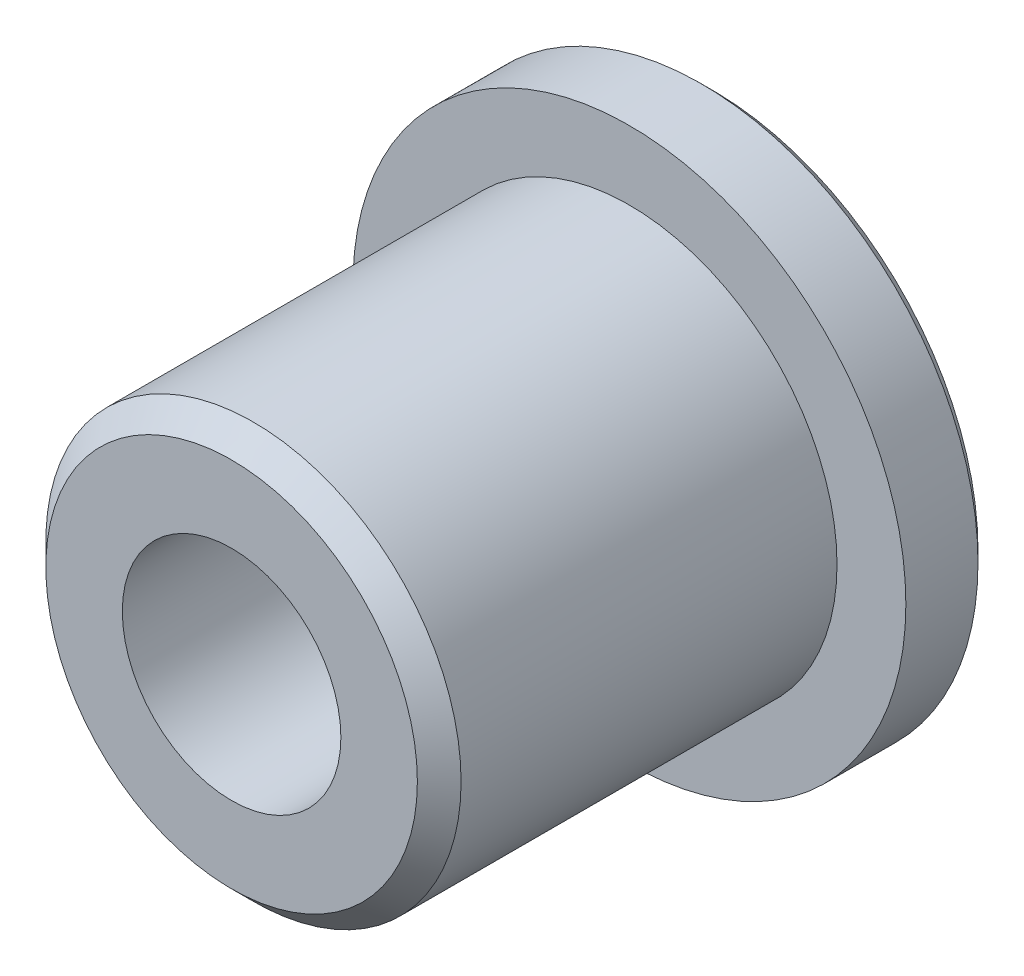
SolidWorks part; units mm, degrees
ref_plane "정면" through (0, 0, 0) normal (0, 0, 1) x (1, 0, 0)
ref_plane "윗면" through (0, 0, 0) normal (0, 1, 0) x (1, 0, 0)
ref_plane "우측면" through (0, 0, 0) normal (1, 0, 0) x (0, 0, -1)
sketch "스케치1" plane through (0, 0, 0) normal (0, 0, 1) x (1, 0, 0)
  circle A0 centre (0, 0) radius 5.875
  circle A1 centre (0, 0) radius 12.65
  dimension "D1" = 11.75
  dimension "D2" = 25.3
extrude "보스-돌출1" add sketch "스케치1" along normal blind 2
sketch "스케치2" plane through (0, 0, 2) normal (0, 0, 1) x (1, 0, 0)
  circle A0 centre (0, 0) radius 5
  circle A1 centre (0, 0) radius 9.5
  dimension "D1" = 19
  dimension "D2" = 10
extrude "보스-돌출2" add sketch "스케치2" along normal blind 20
chamfer "모따기1" distance 0.5 angle 45 1 edges at (5.875, 0, 0)
sketch "스케치3" plane through (0, 0, 2) normal (0, 0, 1) x (1, 0, 0)
  circle A0 centre (0, 0) radius 9.5
  circle A1 centre (0, 0) radius 12.65
  circle A2 centre (0, 0) radius 12.65 construction
  circle A3 centre (0, 0) radius 9.5 construction
extrude "보스-돌출3" add sketch "스케치3" along normal blind 1.8
chamfer "모따기2" distance 1 angle 45 1 edges at (9.5, 0, 22)
chamfer "모따기4" distance 0.5 angle 45 1 edges at (12.65, 0, 0)
sketch "스케치4" plane through (0, 0, 2) normal (0, 0, -1) x (-1, 0, 0)
  circle A0 centre (0, 0) radius 5
  circle A1 centre (0, 0) radius 3
  dimension "D1" = 6
extrude "보스-돌출4" add sketch "스케치4" against normal blind 2
sketch "스케치7" plane through (0, 0, 2) normal (0, 0, -1) x (-1, 0, 0)
  circle A0 centre (0, 0) radius 5.9
  dimension "D1" = 11.8
extrude "컷-돌출1" cut sketch "스케치7" against normal blind 0.3
chamfer "모따기5" distance 0.5 angle 45 1 edges at (-3, 0, 2.3)
sketch "스케치8" plane through (0, 0, 4) normal (0, 0, 1) x (1, 0, 0)
  circle A0 centre (0, 0) radius 3.25
  dimension "D1" = 6.5
extrude "컷-돌출2" cut sketch "스케치8" against normal blind 0.6
chamfer "모따기6" distance 0.5 angle 45 1 edges at (3.25, 0, 3.4)
